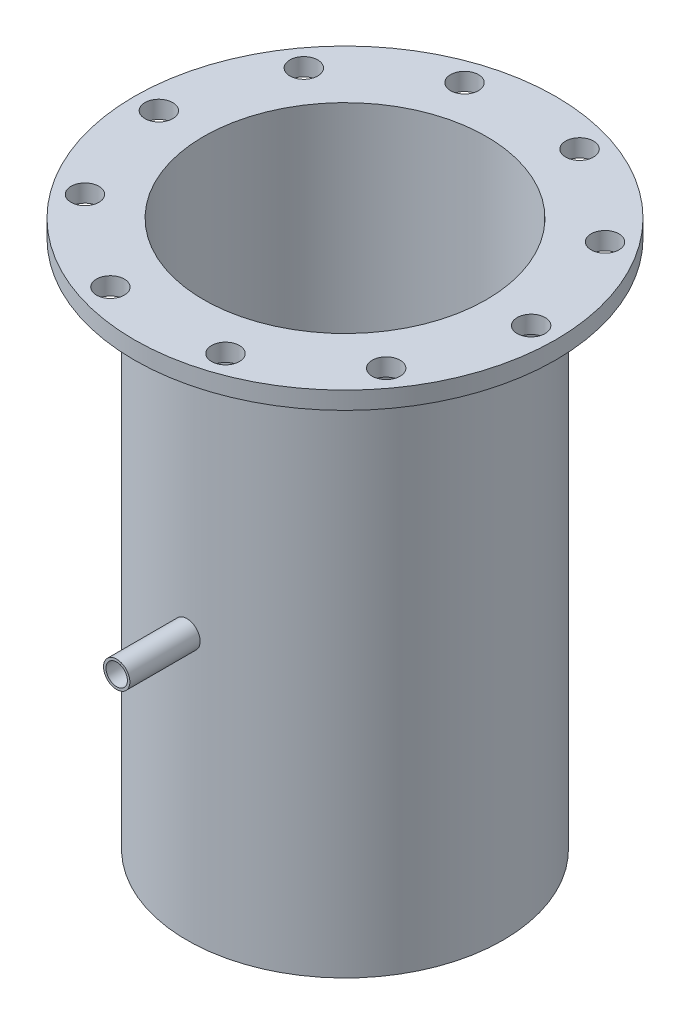
SolidWorks part; units mm, degrees
other "DetailItem1"
other "DetailItem2"
other "Weld Folder"
other "Weld Bead1"
other "Weld Bead2"
material "1023 Carbon Steel Sheet (SS)"
ref_plane "Front Plane" through (0, 0, 0) normal (0, 0, 1) x (1, 0, 0)
ref_plane "Top Plane" through (0, 0, 0) normal (0, 1, 0) x (1, 0, 0)
ref_plane "Right Plane" through (0, 0, 0) normal (1, 0, 0) x (0, 0, -1)
sketch "Sketch1" plane through (0, 0, 0) normal (0, 0, 1) x (1, 0, 0)
  line L0 (0, 0) -> (0, -134.8652) construction
  line L1 (51.1302, 0) -> (51.1302, -184.979)
  line L2 (51.1302, -197.552) -> (57.15, -197.552)
  line L3 (57.15, -197.552) -> (57.15, -8.89)
  line L4 (54.61, -6.35) -> (76.2, -6.35)
  line L5 (76.2, -6.35) -> (76.2, 0)
  line L6 (76.2, 0) -> (51.1302, 0)
  line L7 (51.1302, -184.979) -> (53.848, -184.979)
  line L8 (53.848, -184.979) -> (53.848, -188.027)
  line L9 (53.848, -188.027) -> (51.1302, -188.027)
  line L11 (51.1302, -188.027) -> (51.1302, -197.552)
  line L12 (57.15, -8.89) -> (54.61, -6.35)
  line L15 (-56.1848, -188.027) -> (56.1848, -188.027) construction
  line L16 (-50.1022, -188.027) -> (50.1022, -188.027) construction
  dimension "D1" = 51.1302
  dimension "D2" = 57.15
  dimension "D3" = 76.2
  dimension "D4" = 6.35
  dimension "D5" = 9.525
  dimension "D6" = 53.848
  dimension "D7" = 3.048
  dimension "D9" = 45
  dimension "D10" = 2.54
revolve "Revolve1" add sketch "Sketch1" angle 360 about L0
hole_wizard "Tap Drill for 3/8-16 Tap1" positions "Sketch2" profile "Sketch3" hole size "3/8" standard "ANSI Inch" end condition through all
sketch "Sketch2" plane through (0, 0, 0) normal (0, 1, 0) x (1, 0, 0)
  point P1 (67.31, 0)
  dimension "D1" = 67.31
sketch "Sketch3" plane through (67.31, 0, 0) normal (1, 0, 0) x (0, 0, 1)
  line L0 (0, 0) -> (0, 197.552)
  line L1 (0, 197.552) -> (5.0419, 197.552)
  line L2 (5.0419, 197.552) -> (5.0419, 0)
  line L5 (5.0419, 0) -> (0, 0)
  line L11 (0, -6.35) -> (0, 107.95) construction
  dimension "Thru Hole Dia." = 10.0838
  dimension "Thru Hole Depth" = 197.552
pattern_circular "CirPattern1" count 10 over 360 about axis through (0, 0, 0) along (0, 1, 0) of "Tap Drill for 3/8-16 Tap1"
ref_plane "Plane1" through (0, 0, 57.15) normal (0, 0, 1) x (1, 0, 0)
sketch "Sketch4" plane through (0, 0, 57.15) normal (0, 0, 1) x (1, 0, 0)
  circle A0 centre (0, -101.6) radius 4.7625
  circle A1 centre (0, -101.6) radius 3.8735
  dimension "D1" = 9.525
  dimension "D2" = 0.889
  dimension "D3" = 101.6
extrude "Boss-Extrude1" add sketch "Sketch4" along normal blind 25.4 separate body
hole_wizard "1/8 (0.125) Diameter Hole3" positions "3DSketch2" profile "Sketch11" hole size "1/8" standard "ANSI Inch"
sketch3d "3DSketch2"
  circle A0 centre (0, -101.6, 57.15) radius 4.1349 construction
  circle A1 centre (0, -101.6, 57.15) radius 4.7625 construction
  point P6 (0, -101.6, 61.2849)
  point P19 (0, -101.6, 61.9125)
  point P21 (0, -101.6, 57.15)
  point P24 (0, 0, 0)
sketch "Sketch11" plane through (0, -101.6, 57.15) normal (1, 0, 0) x (0, -1, 0)
  line L0 (0, 0) -> (0, 26.3539)
  line L1 (0, 26.3539) -> (1.5875, 25.4)
  line L2 (1.5875, 25.4) -> (1.5875, 0)
  line L5 (1.5875, 0) -> (0, 0)
  line L10 (0, 26.3539) -> (-1.5875, 25.4) construction
  line L11 (0, -6.35) -> (0, 107.95) construction
  dimension "Hole Dia." = 3.175
  dimension "Hole Depth" = 25.4
  dimension "Drill Angle" = 118
